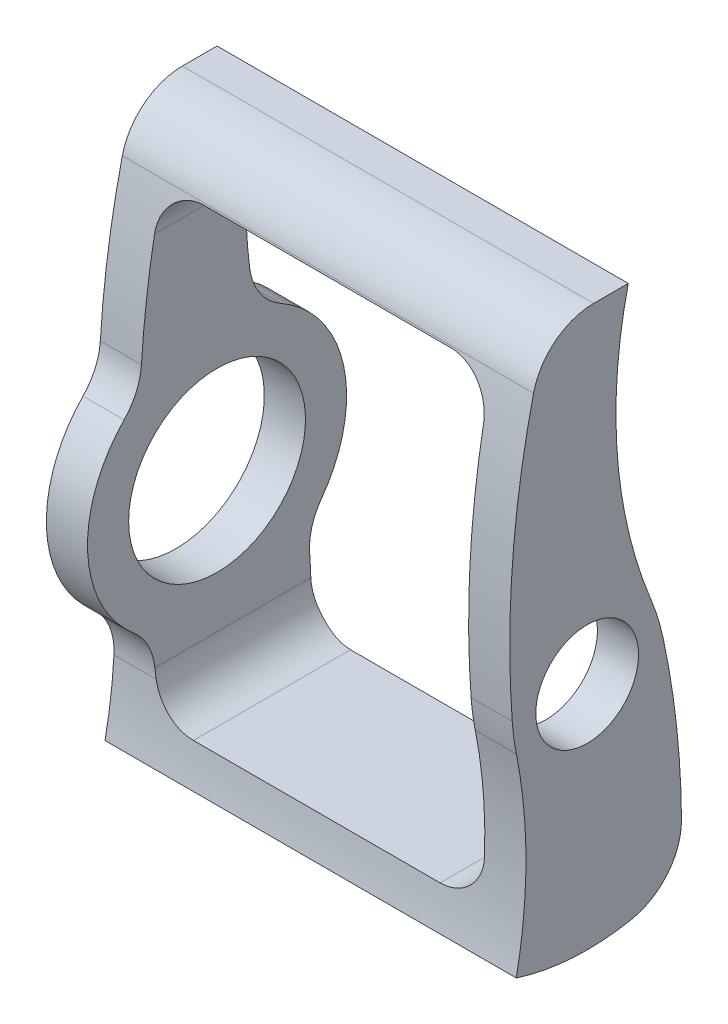
SolidWorks part; units mm, degrees
other "Markup2"
sketch "Sketch9" plane through (31.75, 50.4016, 20.35) normal (0.8402, 0.4575, 0.2911) x (0.3274, 0, -0.9449)
material "AISI 4340 Steel, normalized"
ref_plane "Front Plane" through (0, 0, 0) normal (0, 0, 1) x (1, 0, 0)
ref_plane "Top Plane" through (0, 0, 0) normal (0, 1, 0) x (1, 0, 0)
ref_plane "Right Plane" through (0, 0, 0) normal (1, 0, 0) x (0, 0, -1)
other "Center of Mass"
sketch "Weapon Layout" plane through (0, 0, 0) normal (1, 0, 0) x (0, 0, -1)
  line L0 (-6.35, 50.4016) -> (6.35, 50.4016) construction
  line L1 (-10.9443, -33.834) -> (14.4209, -32.5046) construction
  line L2 (6.35, 50.4016) -> (-5.4537, 0) construction
  line L3 (6.35, 50.4016) -> (0, 0) construction
  line L4 (0, 0) -> (0, -33.2604) construction
  circle A0 centre (0, 0) radius 14 construction
  circle A1 centre (0, 0) radius 50.8 construction
  circle A2 centre (0, 0) radius 17.175 construction
  circle A3 centre (0, 0) radius 20.35 construction
  arc A4 (-6.35, 50.4016) -> (-20.35, 0) centre (77.3756, 0) ccw construction
  arc A5 (23.3803, -26.7932) -> (-23.7089, -26.5029) centre (0, 0) cw construction
  arc A6 (6.35, 50.4016) -> (15.4347, 13.2625) centre (47.4536, 40.7754) ccw construction
  dimension "D1" = 28
  dimension "D2" = 101.6
  dimension "D3" = 3.175
  dimension "D4" = 6.35
  dimension "D5" = 12.7
  dimension "D7" = 6
  dimension "D6" = 15.24
  dimension "D8" = 25.4
  dimension "D9" = 87
sketch "Sketch2" plane through (0, 0, 0) normal (1, 0, 0) x (0, 0, -1)
  line L0 (-6.35, 50.4016) -> (6.35, 50.4016)
  line L1 (-11.3249, -1.5462) -> (0, 0) construction
  line L2 (6.35, 50.4016) -> (-5.4537, 0) construction
  line L3 (-11.5714, 0.7977) -> (-15.24, 50.4016) construction
  arc A0 (-10.9443, -33.834) -> (14.4209, -32.5046) centre (0, 0) ccw
  arc A1 (-23.7089, -26.5029) -> (23.3803, -26.7932) centre (0, 0) ccw construction
  arc A2 (-10.934, -3.8704) -> (-11.5714, 0.7977) centre (26.4248, 3.6078) cw
  arc A3 (9.7952, 6.5275) -> (11.7704, 0.1087) centre (-25.4904, -7.8439) cw
  arc A4 (-11.5714, 0.7977) -> (-6.35, 50.4016) centre (128.3504, 11.1461) cw
  arc A5 (-10.934, -3.8704) -> (-10.9443, -33.834) centre (-85.6518, -18.8267) cw
  arc A6 (6.35, 50.4016) -> (9.7952, 6.5275) centre (76.9323, 33.8717) ccw
  arc A7 (11.7704, 0.1087) -> (14.4209, -32.5046) centre (-112.4323, -26.3999) cw
  circle A9 centre (0, 0) radius 11.43 construction
  point P25 (10.9245, 3.3617)
  dimension "D1" = 127
  dimension "D2" = 38.1
  dimension "D3" = 76.2
  dimension "D4" = 38.1
  dimension "D5" = 22.86
  dimension "D6" = 8.89
extrude "Boss-Extrude2" add sketch "Sketch2" along normal mid plane 63.5
sketch "Sketch3" plane through (0, 0, 0) normal (0, 0, 1) x (1, 0, 0)
  line L0 (31.75, 50.4016) -> (-31.75, 50.4016) construction
  line L1 (-25.4, 42.7816) -> (25.4, 42.7816)
  line L2 (-25.4, 42.7816) -> (-25.4, -27.94)
  line L3 (-25.4, -27.94) -> (25.4, -27.94)
  line L4 (25.4, 42.7816) -> (25.4, -27.94)
  line L6 (-31.75, -35.56) -> (31.75, -35.56) construction
  line L7 (-31.75, 50.4016) -> (-31.75, 0.7977) construction
  dimension "D1" = 7.62
  dimension "D3" = 6.35
  dimension "D4" = 7.62
  dimension "D2" = 6.35
extrude "Cut-Extrude1" cut sketch "Sketch3" against normal through all both and the other way through all
fillet "Fillet1" radius 6.35 4 edges at (-25.4, 42.7816, 1.6753) (25.4, 42.7816, 1.6753) (25.4, -27.94, -2.2798) (-25.4, -27.94, -2.2798)
fillet "Fillet3" radius 9.525 2 edges at (0, -32.5046, -14.4209) (0, 50.4016, 6.35)
sketch "Sketch5" plane through (31.75, 0, 0) normal (1, 0, 0) x (0, 0, -1)
  circle A0 centre (0, 0) radius 7.9375
  circle A1 centre (0, 0) radius 6.35 construction
  dimension "D1" = 12.7
  dimension "D2" = 1.5875
extrude "Cut-Extrude2" cut sketch "Sketch5" against normal up to next
sketch "Sketch6" plane through (-31.75, 0, 0) normal (-1, 0, 0) x (0, 0, 1)
  circle A0 centre (0, 0) radius 20.0025
  circle A1 centre (0, 0) radius 7.9375 construction
  dimension "D1" = 40.005
extrude "Boss-Extrude3" add sketch "Sketch6" against normal up to surface (6.35 mm away) up to face at (-25.4, 4.1451, 0.3502)
fillet "Fillet2" radius 9.525 4 edges at (-28.575, 16.1028, 11.8659) (-28.575, -17.6234, 9.4613) (-28.575, -14.2965, -13.9897) (-28.575, 19.0931, -5.9626)
sketch "Sketch7" plane through (-31.75, 0, 0) normal (-1, 0, 0) x (0, 0, 1)
  circle A0 centre (0, 0) radius 13.6525
  arc A2 (12.9252, -15.2656) -> (14.3489, 13.9359) centre (0, 0) ccw construction
  dimension "D1" = 27.305
extrude "Cut-Extrude3" cut sketch "Sketch7" against normal up to next
equation "\"D1@Weapon Layout\" = 28mm"
equation "\"D1@Sketch6\"=7/8in+1/2in+0.2in"
equation "\"D2@Sketch3\"=\"D3@Sketch3\""
equation "\"D1@Sketch7\"=7/8+0.2"
